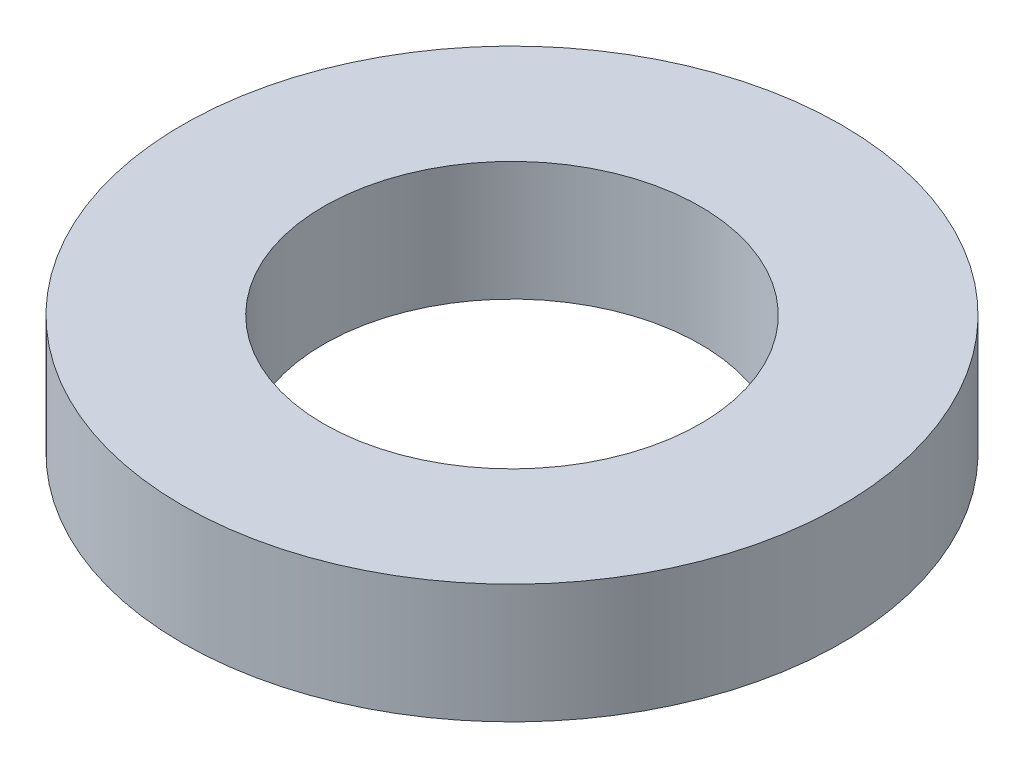
SolidWorks part; units mm, degrees
ref_plane "Front Plane" through (0, 0, 0) normal (0, 0, 1) x (1, 0, 0)
ref_plane "Top Plane" through (0, 0, 0) normal (0, 1, 0) x (1, 0, 0)
ref_plane "Right Plane" through (0, 0, 0) normal (1, 0, 0) x (0, 0, -1)
sketch "Sketch1" plane through (0, 0, 0) normal (0, 1, 0) x (1, 0, 0)
  circle A0 centre (0, 0) radius 52.5
  dimension "FLANGE_OD" = 105
extrude "Boss-Extrude1" add sketch "Sketch1" along normal blind 19
sketch "Sketch2" plane through (0, 0, 0) normal (0, 1, 0) x (1, 0, 0)
  circle A0 centre (0, 0) radius 30
  dimension "BORE_D" = 60
extrude "Cut-Extrude1" cut sketch "Sketch2" along normal through all
sketch "Sketch3" plane through (0, 19, 0) normal (0, 1, 0) x (1, 0, 0)
  circle A0 centre (0, 0) radius 19.4122 construction
  circle A1 centre (-19.4122, 0) radius 2.421
  dimension "BOLT_D" = 4.8421
  dimension "BOLT_PCD" = 38.8244
extrude "Cut-Extrude2" cut sketch "Sketch3" against normal blind 13.2896 rebuild error yes
pattern_circular "CirPattern1" count 3 over 360 rebuild error yes
